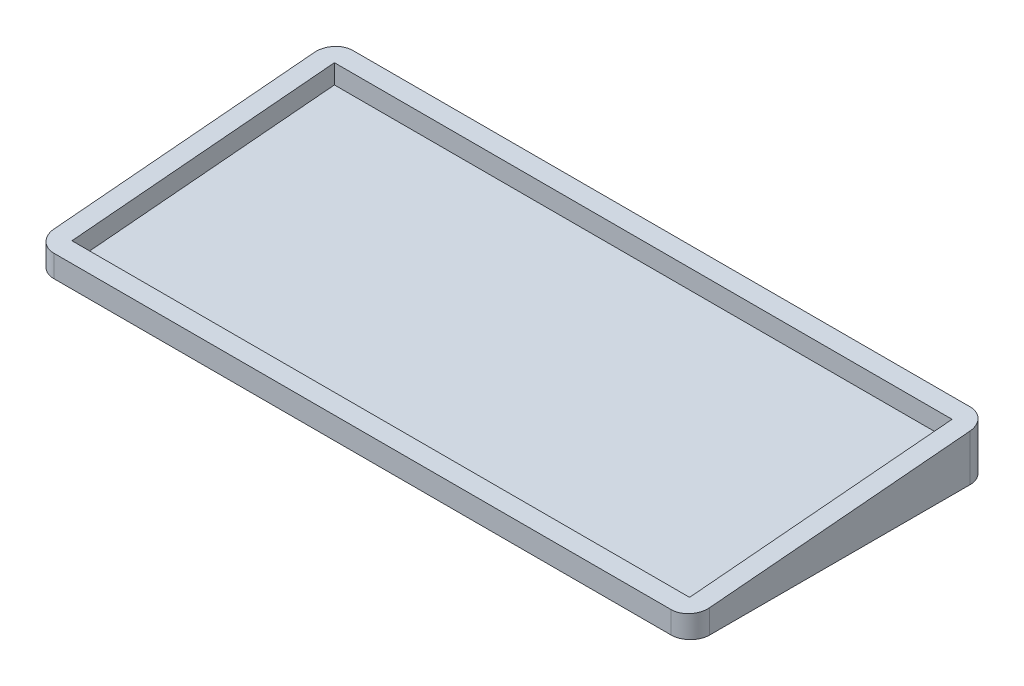
SolidWorks part; units mm, degrees
ref_plane "Front Plane" through (0, 0, 0) normal (0, 0, 1) x (1, 0, 0)
ref_plane "Top Plane" through (0, 0, 0) normal (0, 1, 0) x (1, 0, 0)
ref_plane "Right Plane" through (0, 0, 0) normal (1, 0, 0) x (0, 0, -1)
sketch "Sketch1" plane through (0, 0, 0) normal (0, 1, 0) x (1, 0, 0)
  line L1 (-170, 77.5) -> (170, 77.5)
  line L2 (-170, 77.5) -> (-170, -77.5)
  line L3 (-170, -77.5) -> (170, -77.5)
  line L4 (170, 77.5) -> (170, -77.5)
  line L5 (-170, 77.5) -> (170, -77.5) construction
  line L6 (-170, -77.5) -> (170, 77.5) construction
  point P0 (0, 0)
  dimension "D1" = 340
  dimension "D2" = 155
extrude "Boss-Extrude1" add sketch "Sketch1" along normal blind 25
sketch "Sketch2" plane through (0, 0, 0) normal (1, 0, 0) x (0, 0, -1)
  line L0 (-77.5, 11.4393) -> (77.5, 25)
  line L1 (-77.5, 25) -> (-77.5, 0) construction
  line L2 (77.5, 25) -> (-77.5, 25)
  line L3 (-77.5, 25) -> (77.5, 25) construction
  line L4 (-77.5, 25) -> (-77.5, 11.4393)
  dimension "D1" = 5
extrude "Cut-Extrude1" cut sketch "Sketch2" against normal through all both and the other way through all
fillet "Fillet1" radius 10 4 edges at (170, 12.5, -77.5) (-170, 5.7196, 77.5) (-170, 12.5, -77.5) (170, 5.7196, 77.5)
sketch "Sketch3" plane through (0, 0, 0) normal (0, -1, 0) x (1, 0, 0)
  line L1 (-125, 30) -> (125, 30)
  line L2 (-125, 30) -> (-125, -70)
  line L3 (-125, -70) -> (125, -70)
  line L4 (125, 30) -> (125, -70)
  point P4 (119.4094, -62.9146)
  point P5 (0, 30)
  dimension "D1" = 250
  dimension "D2" = 100
  dimension "D3" = 30
extrude "Cut-Extrude2" cut sketch "Sketch3" against normal blind 3
sketch "Sketch4" plane through (0, 0, 0) normal (0, 1, 0) x (1, 0, 0)
  line L1 (-160.1297, 68.0505) -> (160.1297, 68.0505)
  line L2 (-160.1297, 68.0505) -> (-160.1297, -68.0505)
  line L3 (-160.1297, -68.0505) -> (160.1297, -68.0505)
  line L4 (160.1297, 68.0505) -> (160.1297, -68.0505)
  line L5 (-160.1297, 68.0505) -> (160.1297, -68.0505) construction
  line L6 (-160.1297, -68.0505) -> (160.1297, 68.0505) construction
  point P0 (0, 0)
extrude "Cut-Extrude3" cut sketch "Sketch4" against normal blind 10 from surface starting at face at (0, 18.2196, 0)
